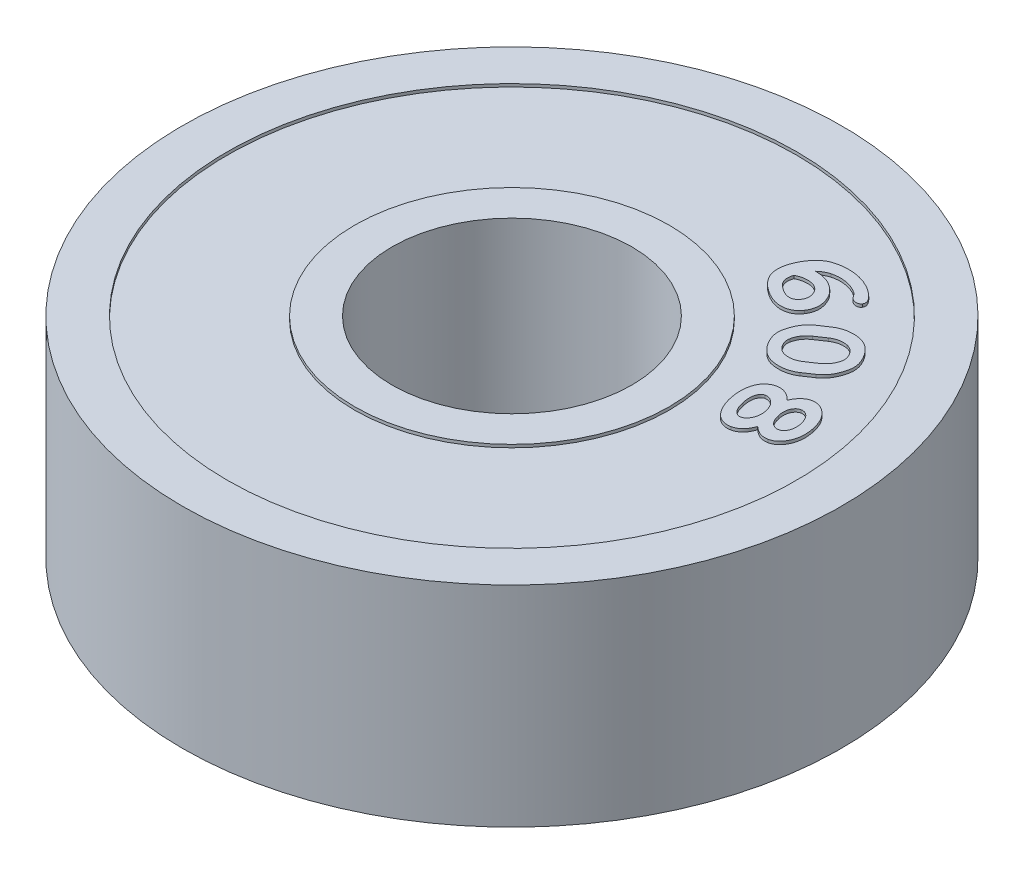
SolidWorks part; units mm, degrees
ref_plane "Front Plane" through (0, 0, 0) normal (0, 0, 1) x (1, 0, 0)
ref_plane "Top Plane" through (0, 0, 0) normal (0, 1, 0) x (1, 0, 0)
ref_plane "Right Plane" through (0, 0, 0) normal (1, 0, 0) x (0, 0, -1)
sketch "Sketch1" plane through (0, 0, 0) normal (0, 1, 0) x (1, 0, 0)
  circle A0 centre (0, 0) radius 11
  circle A1 centre (0, 0) radius 9.5
  circle A2 centre (0, 0) radius 5.25
  circle A3 centre (0, 0) radius 4
  dimension "D1" = 22
  dimension "D2" = 8
  dimension "D3" = 19
  dimension "D4" = 10.5
extrude "Boss-Extrude1" add sketch "Sketch1" along normal blind 7 contours A0 A1 | A1 A2 | A2 A3 region at (-10.6889, 0, 0) region at (-9.2313, 0, 0) region at (-5.1015, 0, 0)
extrude "Cut-Extrude1" cut sketch "Sketch1<3>" against normal blind 0.1 from surface contours A1 A2 region at (-9.2313, 0, 0) starting at face at (0, 7, 11)
sketch "Sketch1<3>" plane through (0, 0, 0) normal (0, 1, 0) x (1, 0, 0) same geometry as "Sketch1"
extrude "Cut-Extrude2" cut sketch "Sketch1<4>" along normal blind 0.1 from surface contours A1 A2 region at (-9.2313, 0, 0) starting at face at (0, 0, 11)
sketch "Sketch1<4>" plane through (0, 0, 0) normal (0, 1, 0) x (1, 0, 0) same geometry as "Sketch1"
sketch "Sketch3" plane through (0, 0, 0) normal (0, 1, 0) x (1, 0, 0)
  circle A0 centre (0, 0) radius 6.3507 construction
  text T0 "<b>608</b>" font "Courier New" height 2
extrude "Boss-Extrude2" add sketch "Sketch3" along normal up to surface (7 mm away) from surface up to face at (0, 7, 9.5) starting at face at (0, 6.9, 5.25)
